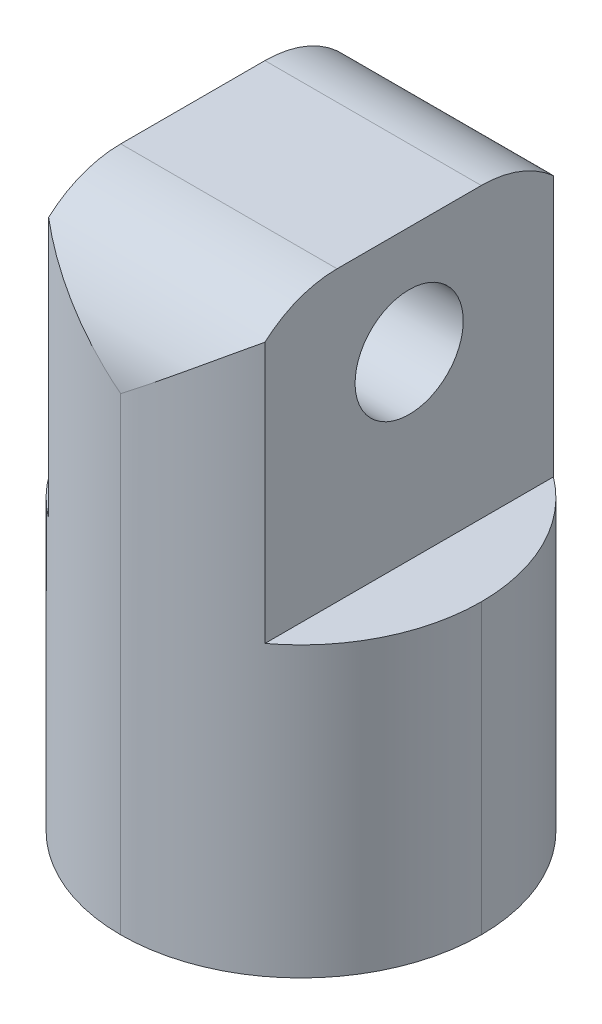
SolidWorks part; units mm, degrees
ref_plane "Alzado" through (0, 0, 0) normal (0, 0, 1) x (1, 0, 0)
ref_plane "Planta" through (0, 0, 0) normal (0, 1, 0) x (1, 0, 0)
ref_plane "Vista lateral" through (0, 0, 0) normal (1, 0, 0) x (0, 0, -1)
sketch "Croquis1" plane through (0, 0, 0) normal (0, 0, 1) x (1, 0, 0)
  line L0 (0, 0) -> (30, 0)
  line L1 (30, 0) -> (30, -40)
  line L2 (0, 0) -> (0, -40)
  line L3 (0, -40) -> (-10, -40)
  line L4 (-10, -40) -> (-10, -80)
  line L8 (-10, -80) -> (40, -80)
  line L9 (40, -80) -> (40, -40)
  line L10 (40, -40) -> (30, -40)
extrude "Saliente-Extruir1" add sketch "Croquis1" along normal blind 50 contours L1 L10 L9 L8 L4 L3 L2 L0
fillet "Redondeo1" radius 15 2 edges at (15, 0, 0) (15, 0, 50)
sketch "Croquis2" plane through (30, 0, 0) normal (1, 0, 0) x (0, 0, -1)
  circle A0 centre (-25, -15) radius 7.5
extrude "Cortar-Extruir1" cut sketch "Croquis2" against normal blind 30
fillet "Redondeo3" radius 25 4 edges at (-10, -60, 50) (-10, -60, 0) (40, -60, 0) (40, -60, 50)
sketch "Croquis3" plane through (0, -80, 0) normal (0, -1, 0) x (1, 0, 0)
  circle A0 centre (15, 25) radius 7.5
extrude "Cortar-Extruir2" cut sketch "Croquis3" against normal blind 7.5
